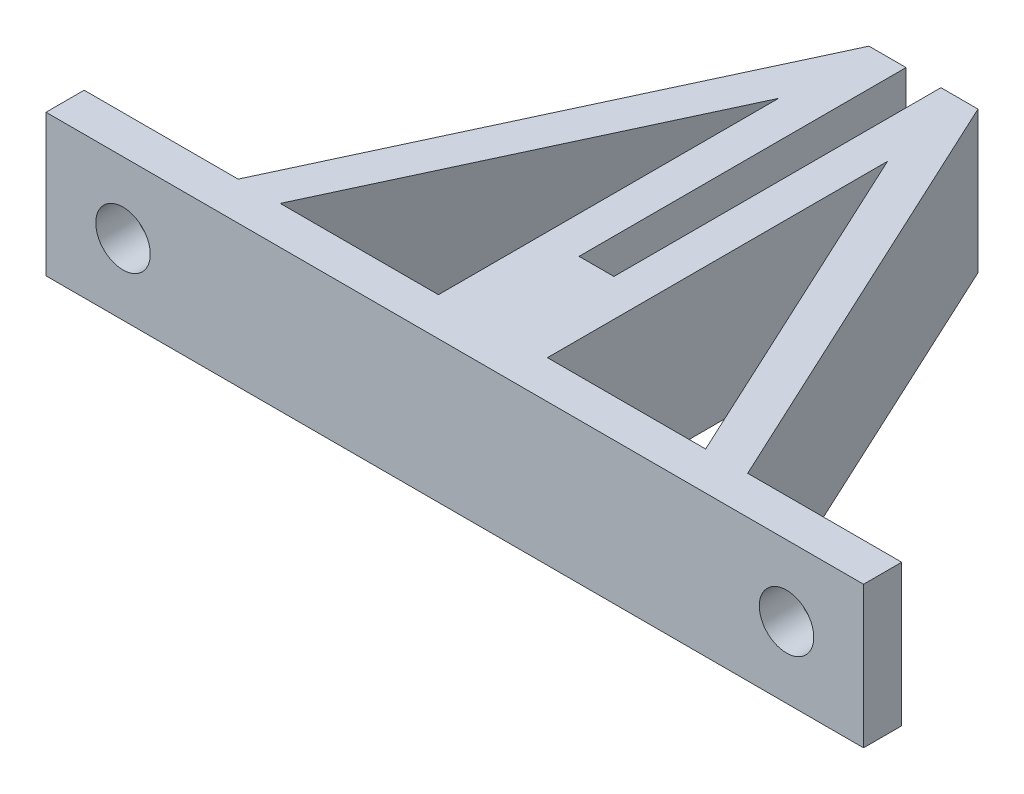
SolidWorks part; units mm, degrees
ref_plane "Front Plane" through (0, 0, 0) normal (0, 0, 1) x (1, 0, 0)
ref_plane "Top Plane" through (0, 0, 0) normal (0, 1, 0) x (1, 0, 0)
ref_plane "Right Plane" through (0, 0, 0) normal (1, 0, 0) x (0, 0, -1)
sketch "Sketch1" plane through (0, 0, 0) normal (0, 1, 0) x (1, 0, 0)
  line L0 (-5.5991, -27.477) -> (-25.5991, -27.477)
  line L1 (-5.5991, 15.523) -> (4.4009, 15.523)
  line L2 (-5.5991, 15.523) -> (-5.5991, -27.477)
  line L3 (-5.5991, -27.477) -> (4.4009, -27.477)
  line L4 (4.4009, 15.523) -> (4.4009, -27.477)
  line L5 (-23.9712, -23.977) -> (-5.5991, 15.523)
  line L6 (4.4009, -27.477) -> (24.4009, -27.477)
  line L7 (4.4009, 15.523) -> (22.773, -23.977)
  line L8 (24.4009, -27.477) -> (36.9009, -27.477)
  line L9 (-25.5991, -27.477) -> (-38.0991, -27.477)
  line L10 (-38.0991, -27.477) -> (-38.0991, -23.977)
  line L11 (-38.0991, -23.977) -> (-23.9712, -23.977)
  line L12 (36.9009, -27.477) -> (36.9009, -23.977)
  line L13 (36.9009, -23.977) -> (22.773, -23.977)
  line L14 (-23.9712, -23.977) -> (-5.5991, -23.977)
  line L15 (18.913, -23.977) -> (4.4009, -23.977)
  line L16 (-20.1111, -23.977) -> (-5.5991, 7.2239)
  line L17 (-22.4256, -28.953) -> (-2.4256, 14.047) construction
  line L18 (4.4009, 7.2239) -> (18.913, -23.977)
  line L19 (1.2274, 14.047) -> (21.2274, -28.953) construction
  line L20 (-25.5991, -27.477) -> (-5.5991, 15.523) construction
  line L21 (4.4009, 15.523) -> (24.4009, -27.477) construction
  line L23 (-2.1991, 15.523) -> (-2.1991, -27.477)
  line L24 (1.0009, 15.523) -> (1.0009, -27.477)
  line L25 (-2.1991, -14.477) -> (1.0009, -14.477)
  point P31 (-0.5991, -14.477)
  dimension "D1" = 43
  dimension "D2" = 10
  dimension "D3" = 20
  dimension "D4" = 20
  dimension "D5" = 12.5
  dimension "D6" = 12.5
  dimension "D7" = 3.5
  dimension "D8" = 3.5
extrude "Boss-Extrude1" add sketch "Sketch1" along normal blind 13 contours L14 L16 L2 L5 | L14 L11 L10 L9 L0 L2 | L23 L1 L2 L3 | L1 L24 L3 L4 | L25 L23 L3 L24 | L4 L18 L15 L6 L8 L12 L13 L7 region at (-21.8491, 0, 25.727) region at (-3.8991, 0, 5.977) region at (-0.5991, 0, 20.977) region at (-13.8579, 0, 6.2206) region at (2.7009, 0, 5.977) region at (16.2927, 0, 15.0887)
extrude "Boss-Extrude2" add sketch "Sketch1<6>" along normal blind 7 contours L23 L25 L24 L1 region at (-0.5991, 0, -0.523)
sketch "Sketch1<6>" plane through (0, 0, 0) normal (0, 1, 0) x (1, 0, 0) same geometry as "Sketch1"
sketch "Sketch2" plane through (0, 0, 23.977) normal (0, 0, -1) x (-1, 0, 0)
  circle A0 centre (31.0351, 6.5) radius 2.5
  circle A1 centre (-29.837, 6.5) radius 2.5
extrude "Cut-Extrude1" cut sketch "Sketch2" against normal blind 7
